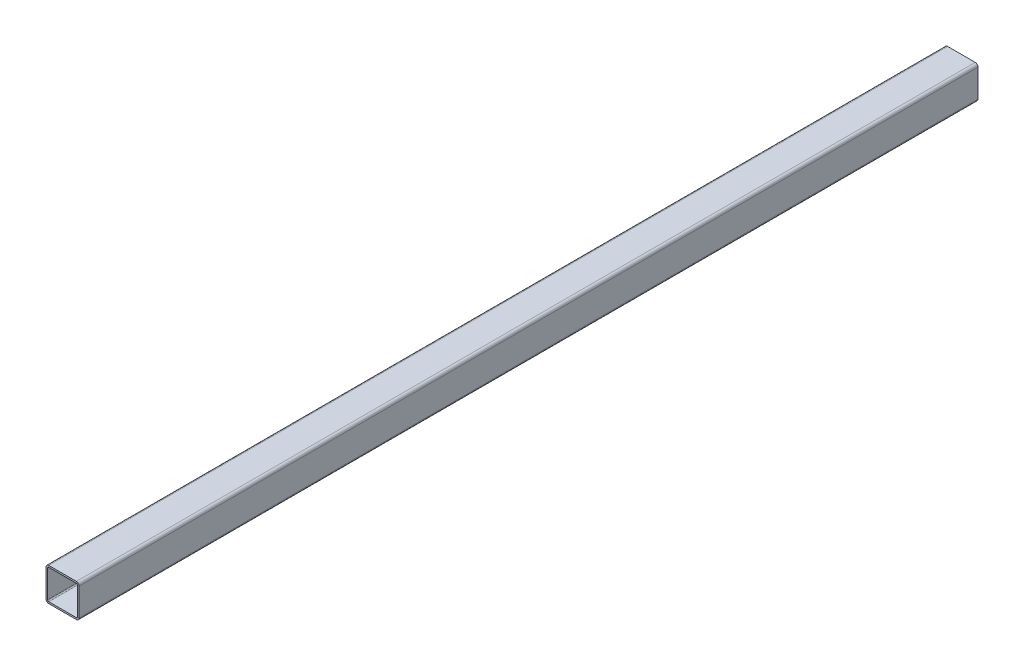
SolidWorks part; units mm, degrees
material "1.0117 (S235J2G4)"
ref_plane "Спереди" through (0, 0, 0) normal (0, 0, 1) x (1, 0, 0)
ref_plane "Сверху" through (0, 0, 0) normal (0, 1, 0) x (1, 0, 0)
ref_plane "Справа" through (0, 0, 0) normal (1, 0, 0) x (0, 0, -1)
sketch "Эскиз1" plane through (0, 0, 0) normal (0, 0, 1) x (1, 0, 0)
  line L1 (-25, -30) -> (25, -30)
  line L2 (-30, -25) -> (-30, 25)
  line L3 (-25, 30) -> (25, 30)
  line L4 (30, -25) -> (30, 25)
  line L5 (-30, 0) -> (30, 0) construction
  arc A0 (25, 30) -> (30, 25) centre (25, 25) cw
  arc A1 (-30, 25) -> (-25, 30) centre (-25, 25) cw
  arc A2 (-25, -30) -> (-30, -25) centre (-25, -25) cw
  arc A3 (25, -30) -> (30, -25) centre (25, -25) ccw
  point P4 (0, -6000)
  point P11 (30, 30)
  point P18 (30, -30)
  dimension "D2" = 5
  dimension "D1" = 60
extrude "Бобышка-Вытянуть1" add sketch "Эскиз1" along normal mid plane 1630
shell "Оболочка1" thickness 3 removed face at (0, 0, 815) removed face at (0, 0, -815)
ref_axis "Ось1" through (0, 0, 1869) along (0, 0, -1)
sketch "Эскиз2" plane through (0, 0, 0) normal (1, 0, 0) x (0, 0, -1)
  line L0 (-815, 0) -> (0, 0) construction
  line L1 (-815, -25) -> (-815, 25) construction
sketch "Эскиз3" plane through (0, 30, 0) normal (0, 1, 0) x (1, 0, 0)
  line L0 (0, -815) -> (0, 815) construction
  line L1 (25, -815) -> (-25, -815) construction
  line L2 (25, 815) -> (-25, 815) construction
sketch "Эскиз4" plane through (0, 0, 0) normal (1, 0, 0) x (0, 0, -1)
  line L0 (815, 0) -> (-815, 0) construction
  line L1 (815, 25) -> (815, -25) construction
  line L2 (-815, 25) -> (-815, -25) construction
  line L3 (0, 0) -> (0, 297.0824) construction
ref_plane "Плоскость1" through (0, 0, 0) normal (0, 0, 1) x (1, 0, 0)
